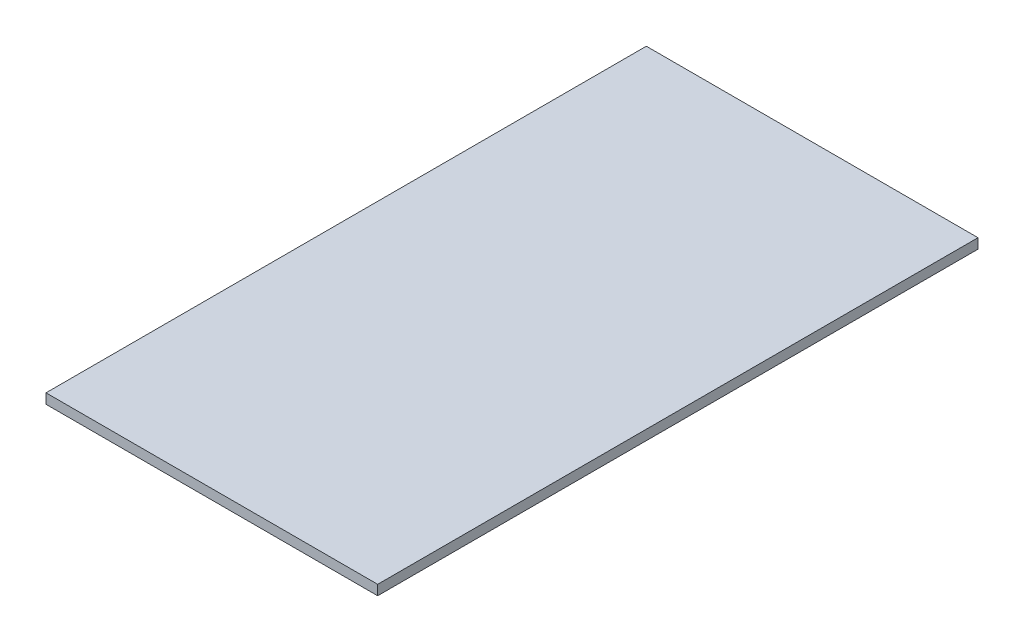
SolidWorks part; units mm, degrees
ref_plane "Front Plane" through (0, 0, 0) normal (0, 0, 1) x (1, 0, 0)
ref_plane "Top Plane" through (0, 0, 0) normal (0, 1, 0) x (1, 0, 0)
ref_plane "Right Plane" through (0, 0, 0) normal (1, 0, 0) x (0, 0, -1)
sketch "Sketch1" plane through (0, 0, 0) normal (0, 1, 0) x (1, 0, 0)
  line L1 (0, 0) -> (100, 0)
  line L2 (0, 0) -> (0, 181)
  line L3 (0, 181) -> (100, 181)
  line L4 (100, 0) -> (100, 181)
  dimension "D1" = 181
  dimension "D2" = 100
extrude "Boss-Extrude1" add sketch "Sketch1" along normal blind 3
